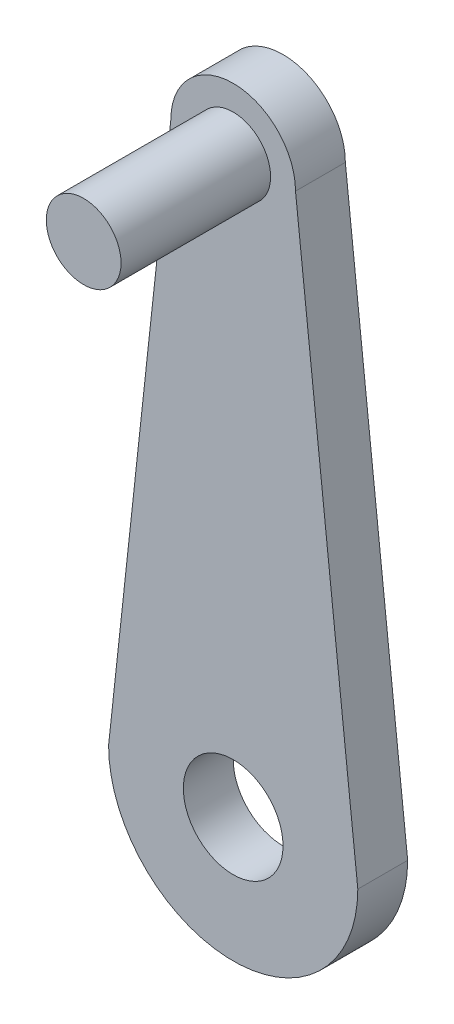
SolidWorks part; units mm, degrees
ref_plane "Front Plane" through (0, 0, 0) normal (0, 0, 1) x (1, 0, 0)
ref_plane "Top Plane" through (0, 0, 0) normal (0, 1, 0) x (1, 0, 0)
ref_plane "Right Plane" through (0, 0, 0) normal (1, 0, 0) x (0, 0, -1)
sketch "Sketch1" plane through (0, 0, 0) normal (0, 0, 1) x (1, 0, 0)
  line L0 (-5, 0) -> (-2.5, 23)
  line L1 (5, 0) -> (2.5, 23)
  arc A0 (-4.8832, 1.0743) -> (4.8832, 1.0743) centre (0, 0) ccw
  arc A1 (2.5, 23) -> (-2.5, 23) centre (0, 23) ccw
  circle A2 centre (0, 23) radius 1.5
  dimension "D1" = 10
  dimension "D2" = 5
  dimension "D3" = 3
  dimension "D4" = 23
extrude "Boss-Extrude1" add sketch "Sketch1" along normal blind 2 contours L1 A1 L0 A0 A2 region at (0, 8.1748, 0)
extrude "Boss-Extrude2" add sketch "Sketch1<3>" along normal blind 8 contours A2
sketch "Sketch1<3>" plane through (0, 0, 0) normal (0, 0, 1) x (1, 0, 0) same geometry as "Sketch1"
sketch "Sketch2" plane through (0, 0, 2) normal (0, 0, 1) x (1, 0, 0)
  circle A0 centre (0, 0) radius 2
  dimension "D1" = 4
extrude "Cut-Extrude1" cut sketch "Sketch2" against normal blind 10
